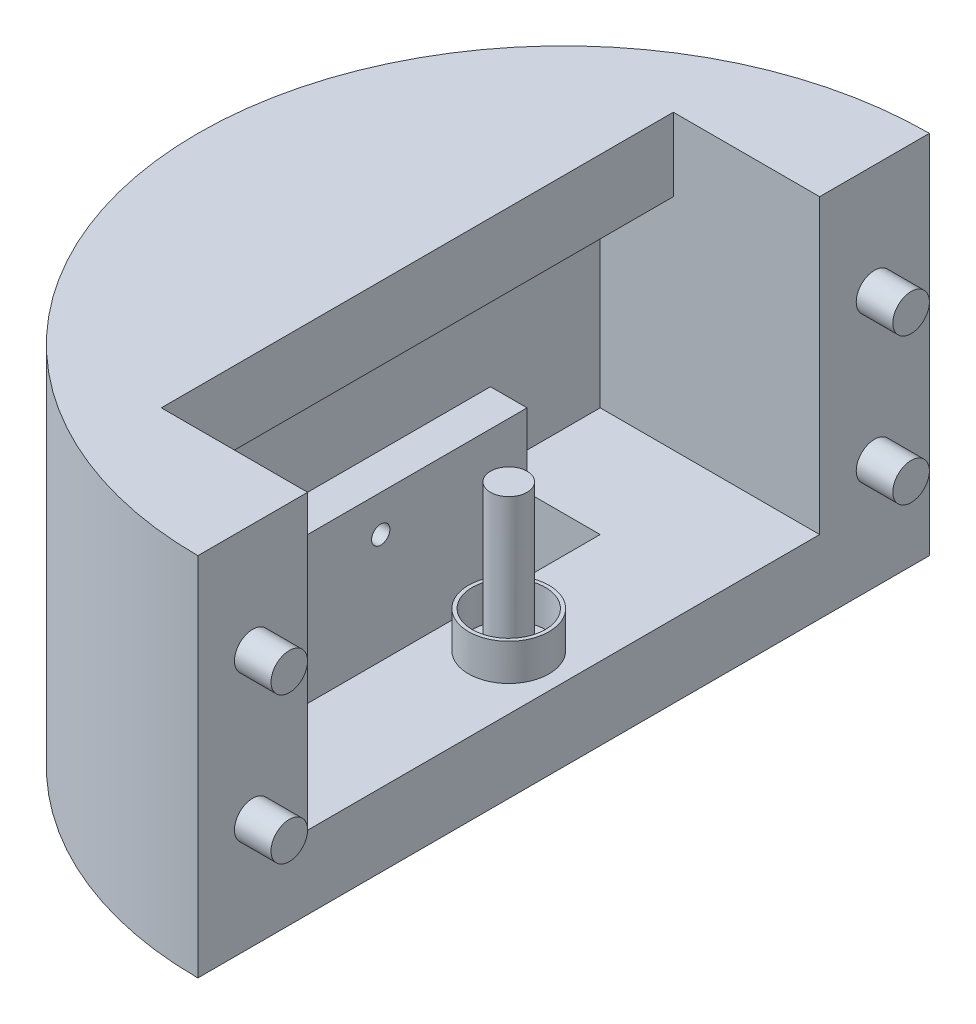
SolidWorks part; units mm, degrees
material "PP Kopolimer"
ref_plane "Front Plane" through (0, 0, 0) normal (0, 0, 1) x (1, 0, 0)
ref_plane "Top Plane" through (0, 0, 0) normal (0, 1, 0) x (1, 0, 0)
ref_plane "Right Plane" through (0, 0, 0) normal (1, 0, 0) x (0, 0, -1)
sketch "Szkic1" plane through (0, 0, 0) normal (0, 1, 0) x (1, 0, 0)
  line L1 (-2.5, -5) -> (2.5, -5)
  line L2 (-2.5, -5) -> (-2.5, 5)
  line L3 (-2.5, 5) -> (2.5, 5)
  line L4 (2.5, -5) -> (2.5, 5)
  line L5 (-2.5, -5) -> (2.5, 5) construction
  line L6 (-2.5, 5) -> (2.5, -5) construction
  point P0 (0, 0)
extrude "Dodanie-wyciągnięcie1" add sketch "Szkic1" along normal blind 1
sketch "Szkic2" plane through (0, 1, 0) normal (0, 1, 0) x (1, 0, 0)
  line L0 (2.5, -5) -> (2.5, 5) construction
  line L1 (-2.5, 5) -> (2.5, 5)
  line L10 (-2.5, 5) -> (-2.5, -5)
  line L15 (-2.5, -5) -> (2.5, -5)
  line L16 (2.5, 3.5) -> (2.5, 5)
  line L17 (-0.5, 3.5) -> (-0.5, -3.5)
  line L18 (2.5, -3.5) -> (2.5, -5)
  line L19 (2.5, 3.5) -> (-0.5, 3.5)
  line L20 (2.5, -3.5) -> (-0.5, -3.5)
extrude "Dodanie-wyciągnięcie4" add sketch "Szkic2" along normal blind 4 contours L17 L20 L18 L15 L10 L1 L16 L19
fillet "Zaokrąglenie2" radius 5 2 edges at (-2.5, 2.5, -5) (-2.5, 2.5, 5)
sketch "Szkic3" plane through (0, 1, 0) normal (0, 1, 0) x (1, 0, 0)
  line L0 (-0.5, 0) -> (0, 0) construction
  line L1 (-0.5, 3.5) -> (-0.5, -3.5) construction
  line L2 (0, 0) -> (0, 2) construction
  line L4 (0, 2) -> (1, 2)
  line L5 (0, 2) -> (0, -2)
  line L6 (0, -2) -> (1, -2)
  line L7 (1, 2) -> (1, -2)
extrude "Wytnij-wyciągnięcie1" cut sketch "Szkic3" against normal blind 4
sketch "Szkic4" plane through (0, 1, 0) normal (0, 1, 0) x (1, 0, 0)
  line L0 (-0.5, 3.5) -> (-0.5, -3.5) construction
  line L1 (0, 2) -> (-0.5, 2)
  line L2 (0, 2) -> (0, -2)
  line L3 (0, -2) -> (-0.5, -2)
  line L4 (-0.5, 2) -> (-0.5, -2)
extrude "Dodanie-wyciągnięcie5" add sketch "Szkic4" along normal blind 1
sketch "Szkic5" plane through (0, 1, 0) normal (0, 1, 0) x (1, 0, 0)
  line L0 (1, 0) -> (2.5, 0) construction
  line L1 (1, -2) -> (1, 2) construction
  line L2 (2.5, -3.5) -> (2.5, 3.5) construction
  circle A0 centre (1.75, 0) radius 0.25
extrude "Dodanie-wyciągnięcie6" add sketch "Szkic5" along normal blind 2
sketch "Szkic6" plane through (0, 1, 0) normal (0, 1, 0) x (1, 0, 0)
  circle A0 centre (1.75, 0) radius 0.5
  circle A1 centre (1.75, 0) radius 0.55
extrude "Dodanie-wyciągnięcie7" add sketch "Szkic6" along normal blind 0.5
sketch "Szkic7" plane through (-0.5, 0, 0) normal (1, 0, 0) x (0, 0, -1)
  line L0 (-3.5, 5) -> (-3.5, 1) construction
  line L1 (3.5, 5) -> (-3.5, 5)
  line L2 (3.5, 5) -> (3.5, 4)
  line L3 (3.5, 4) -> (-3.5, 4)
  line L4 (-3.5, 5) -> (-3.5, 4)
extrude "Dodanie-wyciągnięcie8" add sketch "Szkic7" along normal blind 1
sketch "Szkic11" plane through (2.5, 0, 0) normal (1, 0, 0) x (0, 0, -1)
  line L0 (-4.25, 5) -> (-4.25, 3.5031)
  line L1 (-3.5, 5) -> (-5, 5) construction
  line L2 (-4.25, 3.5031) -> (-4.25, 1.5031)
  line L3 (4.25, 5) -> (4.25, 3.5031) construction
  line L4 (3.5, 5) -> (5, 5) construction
  line L5 (4.25, 3.5031) -> (4.25, 1.5031) construction
  circle A0 centre (-4.25, 3.5031) radius 0.25
  circle A1 centre (-4.25, 1.5031) radius 0.25
  circle A2 centre (4.25, 3.5031) radius 0.25
  circle A3 centre (4.25, 1.5031) radius 0.25
  point P14 (0, 0)
  point P15 (0, 0)
extrude "Dodanie-wyciągnięcie10" add sketch "Szkic11" along normal blind 0.5 contours A3 | A2 | A0 | A1
sketch "Szkic12" plane through (0, 0, 0) normal (1, 0, 0) x (0, 0, -1)
  line L0 (0, 0) -> (0, 1.5) construction
  circle A0 centre (0, 1.5) radius 0.125
extrude "Wytnij-wyciągnięcie2" cut sketch "Szkic12" against normal blind 1
